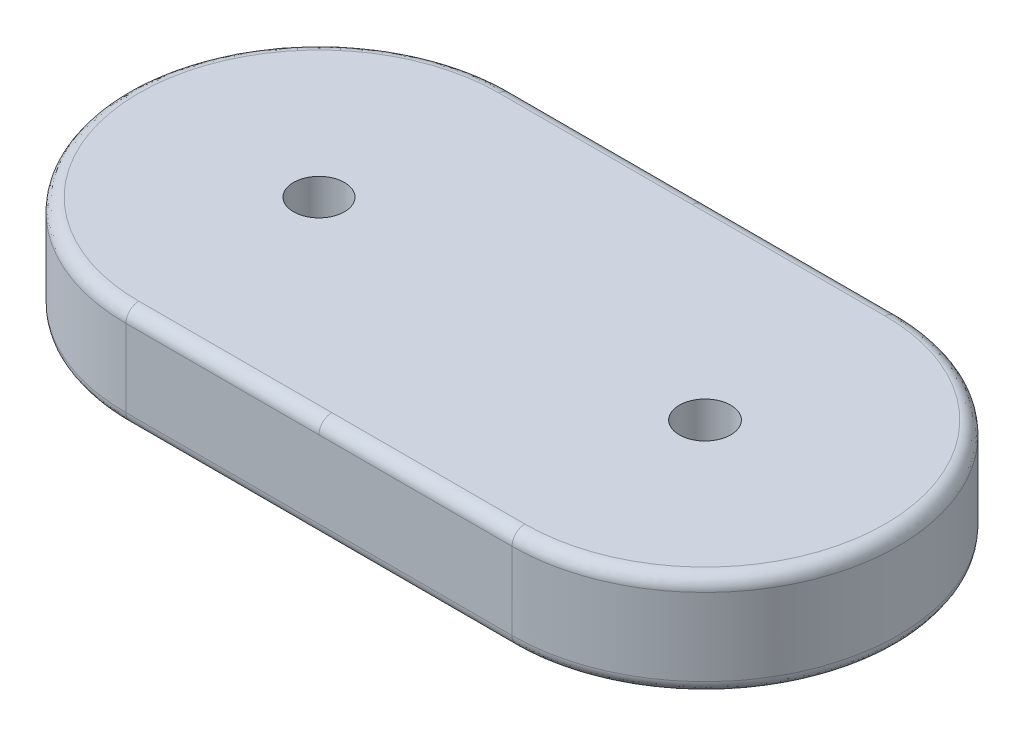
SolidWorks part; units mm, degrees
ref_plane "Front Plane" through (0, 0, 0) normal (0, 0, 1) x (1, 0, 0)
ref_plane "Top Plane" through (0, 0, 0) normal (0, 1, 0) x (1, 0, 0)
ref_plane "Right Plane" through (0, 0, 0) normal (1, 0, 0) x (0, 0, -1)
sketch "Sketch2" plane through (0, 0, 0) normal (0, 1, 0) x (1, 0, 0)
  line L0 (0, 0) -> (30, 0)
  line L1 (0, 0) -> (0, 15) construction
  line L2 (0, -55) -> (0, 55) construction
  line L3 (30, 0) -> (30, 15) construction
  line L4 (0, 15) -> (30, 15) construction
  line L5 (30, 15) -> (30, 20)
  line L6 (30, 20) -> (0, 20)
  line L7 (0, 20) -> (0, 15)
  line L8 (0, 7.5) -> (-7.5, 7.5) construction
  line L9 (30, 7.5) -> (37.5, 7.5) construction
  line L10 (-55, 0) -> (55, 0) construction
  line L11 (-7.5, 15) -> (0, 15)
  line L12 (30, 15) -> (37.5, 15)
  line L13 (37.5, 0) -> (-7.5, 0)
  ellipse E0 centre (-7.5, 7.5) end of major axis (0, 7.5) minor radius 7.5 (-7.5, 0) -> (-7.5, 15) cw
  ellipse E1 centre (37.5, 7.5) end of major axis (37.5, 0) minor radius 7.5 (37.5, 0) -> (37.5, 15) ccw
extrude "Boss-Extrude1" add sketch "Sketch2" along normal blind 4 contours L13 E1 L12 L5 L6 L7 L11 E0 L0 region at (15, 0, -8.9944)
sketch "Sketch3" plane through (0, 0, 0) normal (0, 1, 0) x (1, 0, 0)
  line L0 (30, 20) -> (30, 17.5) construction
  line L1 (30, 15) -> (30, 20) construction
  line L2 (30, 17.5) -> (15, 17.5) construction
  circle A0 centre (15, 17.5) radius 0.49
extrude "Cut-Extrude2" cut sketch "Sketch3" against normal through all both and the other way through all
sketch "Sketch4" plane through (0, 0, 0) normal (0, 1, 0) x (1, 0, 0)
  line L0 (0, 0) -> (0, 7.5) construction
  line L1 (0, -55) -> (0, 55) construction
  line L2 (0, 7.5) -> (-7.5, 7.5) construction
  line L3 (30, 15) -> (30, 7.5) construction
  line L4 (30, 7.5) -> (37.5, 7.5) construction
  circle A0 centre (-7.5, 7.5) radius 0.99
  circle A1 centre (37.5, 7.5) radius 0.98
extrude "Cut-Extrude3" cut sketch "Sketch4" against normal through all both and the other way through all
fillet "Fillet1" radius 0.5 5 edges at (33.75, 4, -15) (45, 4, -7.5) (-3.75, 4, -15) (-15, 4, -7.5) (15, 4, 0)
fillet "Fillet2" radius 0.5 1 edges at (15, 4, -20)
fillet "Fillet3" radius 0.5 3 edges at (0, 1.75, -20) (0, 3.8536, -19.8536) (0, 4, -17)
fillet "Fillet4" radius 0.5 3 edges at (30, 1.75, -20) (30, 3.8536, -19.8536) (30, 4, -17)
sketch "Sketch5" plane through (0, 0, 0) normal (1, 0, 0) x (0, 0, -1)
  line L0 (0, 0) -> (20, 0)
  line L1 (20, 0) -> (20, 4.1097)
  line L2 (20, 4.1097) -> (0, 4.2628)
  line L3 (0, 2.2) -> (0, -2.2) construction
  line L4 (0, 4.2628) -> (0, 0)
extrude "Cut-Extrude4" cut sketch "Sketch5" along normal through all
sketch "Sketch6" plane through (0, 0, 0) normal (0, 1, 0) x (1, 0, 0)
  line L0 (0, 15) -> (15, 15)
  line L1 (15, 15) -> (15, 0)
  line L2 (15, 0) -> (0, 0)
  line L3 (0, 0) -> (0, 15)
extrude "Boss-Extrude2" add sketch "Sketch6" along normal blind 4
sketch "Sketch7" plane through (0, 0, 0) normal (0, 1, 0) x (1, 0, 0)
  line L0 (7.5, 15) -> (7.5, 0) construction
  line L1 (15, 15) -> (0, 15) construction
  line L2 (0, 0) -> (15, 0) construction
  line L3 (7.5, 7.5) -> (15, 7.5) construction
  line L4 (15, 0) -> (15, 15) construction
  line L5 (7.5, 15) -> (15, 15)
  line L6 (15, 15) -> (15, 0)
  line L7 (15, 0) -> (7.5, 0)
  ellipse E0 centre (7.5, 7.5) end of major axis (15, 7.5) minor radius 7.5 (7.5, 15) -> (7.5, 0) cw
extrude "Cut-Extrude5" cut sketch "Sketch7" along normal through all contours L5 E0 L6 | L6 E0 L7 region at (13.3247, 0, -1.6753) region at (13.3247, 0, -13.3247)
sketch "Sketch8" plane through (0, 0, 0) normal (0, 1, 0) x (1, 0, 0)
  line L0 (7.5, 15) -> (7.5, 0) construction
  circle A0 centre (7.5, 7.5) radius 1
extrude "Cut-Extrude8" cut sketch "Sketch8" along normal through all
fillet "Fillet5" radius 0.5 7 edges at (15, 0, -7.5) (0, 0, -15) (-15, 0, -7.5) (0, 0, 0) (3.75, 4, 0) (15, 4, -7.5) (3.75, 4, -15)
